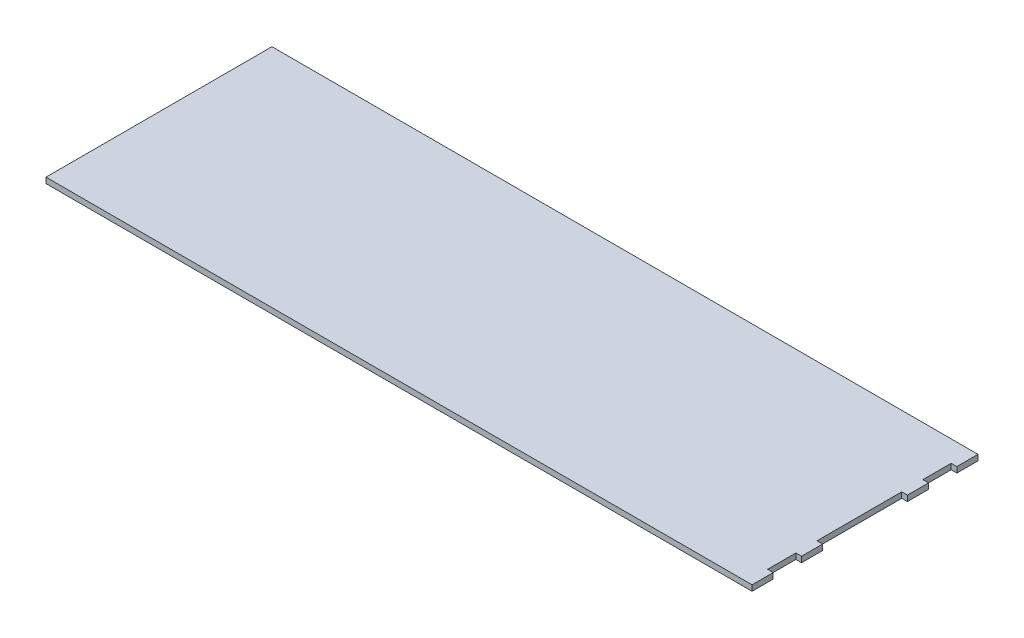
SolidWorks part; units mm, degrees
ref_plane "Front Plane" through (0, 0, 0) normal (0, 0, 1) x (1, 0, 0)
ref_plane "Top Plane" through (0, 0, 0) normal (0, 1, 0) x (1, 0, 0)
ref_plane "Right Plane" through (0, 0, 0) normal (1, 0, 0) x (0, 0, -1)
sketch "Sketch1" plane through (0, 0, 0) normal (0, 1, 0) x (1, 0, 0)
  line L1 (317.5, -101.6) -> (-317.5, -101.6)
  line L2 (317.5, -101.6) -> (317.5, 101.6)
  line L3 (317.5, 101.6) -> (-317.5, 101.6)
  line L4 (-317.5, -101.6) -> (-317.5, 101.6)
  line L5 (317.5, -101.6) -> (-317.5, 101.6) construction
  line L6 (317.5, 101.6) -> (-317.5, -101.6) construction
  point P0 (0, 0)
  dimension "D1" = 203.2
  dimension "D2" = 635
extrude "Boss-Extrude1" add sketch "Sketch1" along normal blind 5.08
sketch "Sketch2" plane through (0, 5.08, 0) normal (0, 1, 0) x (1, 0, 0)
  line L0 (317.5, -101.6) -> (317.5, 101.6) construction
  line L1 (317.5, 82.55) -> (312.42, 82.55)
  line L2 (317.5, 82.55) -> (317.5, 57.15)
  line L3 (317.5, 57.15) -> (312.42, 57.15)
  line L4 (312.42, 82.55) -> (312.42, 57.15)
  line L5 (317.5, 101.6) -> (-317.5, 101.6) construction
  line L6 (-317.5, -101.6) -> (317.5, -101.6) construction
  line L7 (317.5, -57.15) -> (312.42, -57.15)
  line L8 (317.5, -57.15) -> (317.5, -82.55)
  line L9 (317.5, -82.55) -> (312.42, -82.55)
  line L10 (312.42, -57.15) -> (312.42, -82.55)
  line L12 (317.5, 38.1) -> (312.42, 38.1)
  line L13 (317.5, 38.1) -> (317.5, -38.1)
  line L14 (317.5, -38.1) -> (312.42, -38.1)
  line L15 (312.42, 38.1) -> (312.42, -38.1)
  dimension "D1" = 5.08
  dimension "D2" = 25.4
  dimension "D3" = 19.05
  dimension "D4" = 5.08
  dimension "D5" = 19.05
  dimension "D6" = 25.4
  dimension "D7" = 5.08
  dimension "D8" = 76.2
  dimension "D9" = 19.05
  dimension "D10" = 19.05
extrude "Cut-Extrude1" cut sketch "Sketch2" against normal up to surface (5.08 mm away) up to face at (0, 0, 0)
